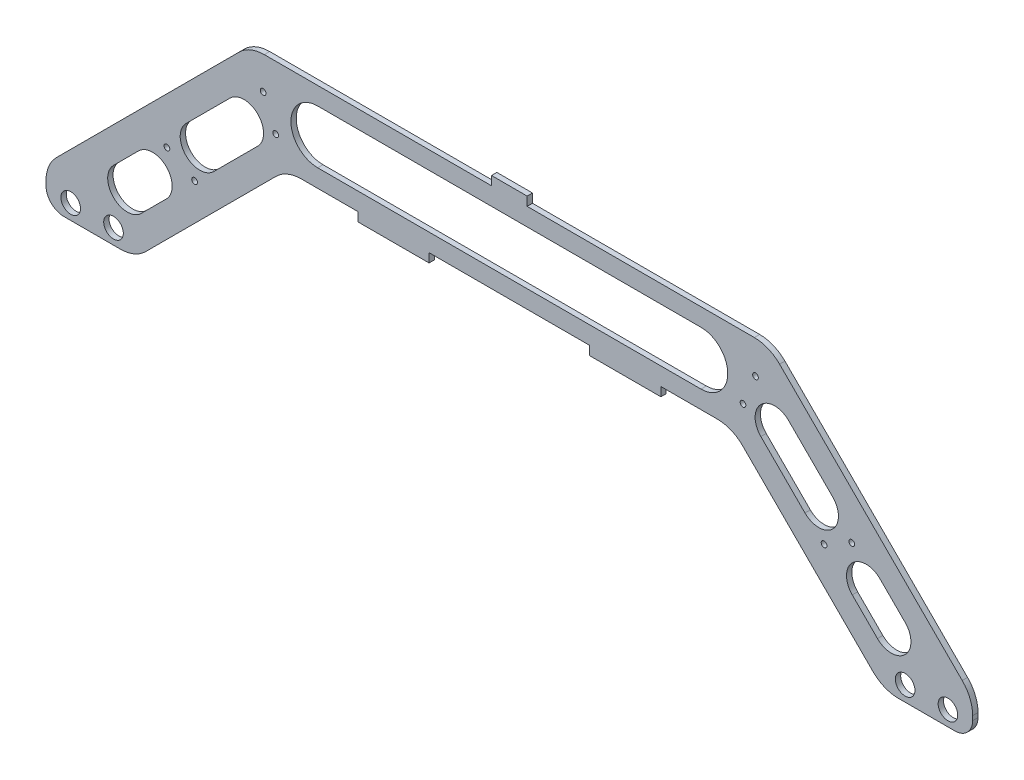
SolidWorks part; units mm, degrees
ref_plane "前视基准面" through (0, 0, 0) normal (0, 0, 1) x (1, 0, 0)
ref_plane "上视基准面" through (0, 0, 0) normal (0, 1, 0) x (1, 0, 0)
ref_plane "右视基准面" through (0, 0, 0) normal (1, 0, 0) x (0, 0, -1)
sketch "草图1" plane through (0, 0, 0) normal (0, 0, 1) x (1, 0, 0)
  line L0 (-125, 25) -> (-10, 25)
  line L1 (-125, 25) -> (-125, -25) construction
  line L2 (125, 25) -> (125, -25) construction
  line L3 (-116.7157, -25) -> (-85, -25)
  line L4 (-125, 25) -> (125, -25) construction
  line L5 (125, 25) -> (-125, -25) construction
  line L6 (0, 25) -> (0, 30) construction
  line L7 (-10, 25) -> (-10, 30)
  line L9 (-10, 30) -> (10, 30)
  line L10 (10, 25) -> (10, 30)
  line L11 (0, 25) -> (10, 30) construction
  line L12 (-10, 30) -> (0, 25) construction
  line L13 (-130.8579, -30.8579) -> (-203.9949, -103.9949)
  line L19 (10, 25) -> (125, 25)
  line L20 (-167.4264, -67.4264) -> (-202.7817, -32.0711) construction
  line L21 (125, 25) -> (125, -25) construction
  line L22 (-202.7817, -32.0711) -> (-151.5685, 19.1421)
  line L23 (-137.4264, 25) -> (-125, 25)
  line L24 (-202.7817, -32.0711) -> (-253.9949, -83.2843)
  line L25 (-259.8528, -97.4264) -> (-259.8528, -99.8528)
  line L26 (259.8528, -97.4264) -> (259.8528, -99.8528)
  line L27 (202.7817, -32.0711) -> (253.9949, -83.2843)
  line L28 (137.4264, 25) -> (125, 25)
  line L29 (202.7817, -32.0711) -> (151.5685, 19.1421)
  line L30 (167.4264, -67.4264) -> (202.7817, -32.0711) construction
  line L31 (218.1371, -109.8528) -> (249.8528, -109.8528)
  line L32 (130.8579, -30.8579) -> (203.9949, -103.9949)
  line L33 (-249.8528, -109.8528) -> (-218.1371, -109.8528)
  line L34 (-233.9949, -109.8528) -> (-233.9949, -63.2843) construction
  line L35 (-233.9949, -109.8528) -> (-245.9949, -109.8528)
  line L36 (-245.9949, -109.8528) -> (-245.9949, -101.3528)
  line L37 (-245.9949, -101.3528) -> (-245.9949, -106.8528)
  line L38 (-125, -25) -> (-85, -25) construction
  line L39 (0, -25) -> (-45, -25)
  line L40 (-65, -25) -> (-65, -30)
  line L41 (-85, -30) -> (-45, -30)
  line L42 (-85, -30) -> (-85, -25)
  line L43 (-45, -30) -> (-45, -25)
  line L44 (45, -30) -> (45, -25)
  line L45 (85, -30) -> (85, -25)
  line L46 (85, -30) -> (45, -30)
  line L47 (65, -25) -> (65, -30)
  line L48 (-45, -25) -> (45, -25)
  line L49 (-45, -25) -> (45, -25) construction
  line L50 (85, -25) -> (116.7157, -25)
  line L51 (85, -25) -> (125, -25) construction
  arc A0 (-249.8528, -109.8528) -> (-259.8528, -99.8528) centre (-249.8528, -99.8528) cw
  arc A1 (-116.7157, -25) -> (-130.8579, -30.8579) centre (-116.7157, -45) ccw
  arc A2 (-137.4264, 25) -> (-151.5685, 19.1421) centre (-137.4264, 5) ccw
  arc A3 (-253.9949, -83.2843) -> (-259.8528, -97.4264) centre (-239.8528, -97.4264) ccw
  arc A4 (-203.9949, -103.9949) -> (-218.1371, -109.8528) centre (-218.1371, -89.8528) cw
  arc A5 (203.9949, -103.9949) -> (218.1371, -109.8528) centre (218.1371, -89.8528) ccw
  arc A6 (253.9949, -83.2843) -> (259.8528, -97.4264) centre (239.8528, -97.4264) cw
  arc A7 (137.4264, 25) -> (151.5685, 19.1421) centre (137.4264, 5) cw
  arc A8 (116.7157, -25) -> (130.8579, -30.8579) centre (116.7157, -45) cw
  arc A9 (249.8528, -109.8528) -> (259.8528, -99.8528) centre (249.8528, -99.8528) ccw
  circle A12 centre (-245.9949, -101.3528) radius 5.5
  circle A13 centre (-221.9949, -101.3528) radius 5.5
  circle A14 centre (221.9949, -101.3528) radius 5.5
  circle A15 centre (245.9949, -101.3528) radius 5.5
  point P1 (0, 0)
  point P20 (-259.8528, -109.8528)
  point P30 (-209.8528, -109.8528)
  point P48 (209.8528, -109.8528)
  point P49 (259.8528, -109.8528)
  point P68 (-65, -30)
  point P76 (65, -30)
  dimension "D7" = 10
  dimension "D8" = 20
  dimension "D11" = 5.5
  dimension "D12" = 65
  dimension "D1" = 250
  dimension "D2" = 50
  dimension "D3" = 5
  dimension "D4" = 50
  dimension "D5" = 120
  dimension "D6" = 50
  dimension "D9" = 12
  dimension "D10" = 8.5
  dimension "D13" = 5
  dimension "D14" = 20
extrude "凸台-拉伸1" add sketch "草图1" along normal mid plane 3 contours A12 L33 A4 L13 A1 L3 A8 L32 A5 L31 A9 L26 A6 L27 L29 A7 L28 L19 L10 L9 L7 L0 L23 A2 L22 L24 A3 L25 A0 A13 A14 A15 region at (-67.5, 19.6181, 0)
sketch "草图2" plane through (0, 0, 1.5) normal (0, 0, 1) x (1, 0, 0)
  line L0 (-107.5, 0) -> (107.5, 0) construction
  line L1 (-158.1371, 55) -> (-116.7157, -45)
  line L2 (-107.5, 15) -> (107.5, 15)
  line L3 (-107.5, -15) -> (107.5, -15)
  line L4 (-221.9949, -101.3528) -> (-245.9949, -101.3528)
  line L5 (-245.9949, -101.3528) -> (-138.0754, 6.5668) construction
  line L6 (-221.9949, -101.3528) -> (-131.0459, -10.4038) construction
  line L7 (0, -15) -> (0, 15) construction
  line L8 (-228.3883, -57.6777) -> (-193.033, -93.033)
  line L9 (-202.7817, -32.0711) -> (-253.9949, -83.2843) construction
  line L10 (-130.8579, -30.8579) -> (-203.9949, -103.9949) construction
  line L11 (-210.7107, -75.3553) -> (-161.2132, -25.8579)
  line L12 (-148.8388, -13.4835) -> (-173.5876, -38.2322) construction
  line L13 (-210.7107, -75.3553) -> (-207.1751, -71.8198)
  line L14 (-141.0607, -21.2617) -> (-165.8094, -46.0104)
  line L15 (-156.617, -5.7053) -> (-181.3657, -30.4541)
  line L16 (-214.2462, -78.8909) -> (-200.1041, -64.7487) construction
  line L17 (148.8388, -13.4835) -> (173.5876, -38.2322) construction
  line L18 (-222.0244, -71.1127) -> (-207.8823, -56.9706)
  line L19 (-206.468, -86.669) -> (-192.3259, -72.5269)
  line L20 (141.0607, -21.2617) -> (165.8094, -46.0104)
  line L21 (156.617, -5.7053) -> (181.3657, -30.4541)
  line L22 (214.2462, -78.8909) -> (200.1041, -64.7487) construction
  line L23 (222.0244, -71.1127) -> (207.8823, -56.9706)
  line L24 (206.468, -86.669) -> (192.3259, -72.5269)
  arc A0 (-107.5, 15) -> (-107.5, -15) centre (-107.5, 0) ccw
  arc A1 (107.5, -15) -> (107.5, 15) centre (107.5, 0) ccw
  circle A2 centre (-138.0754, 6.5668) radius 1.6
  circle A3 centre (-131.0459, -10.4038) radius 1.6
  circle A6 centre (-176.5204, -55.8783) radius 1.6
  circle A7 centre (-192.0352, -47.393) radius 1.6
  circle A8 centre (131.0459, -10.4038) radius 1.6
  circle A9 centre (138.0754, 6.5668) radius 1.6
  circle A10 centre (176.5204, -55.8783) radius 1.6
  circle A11 centre (192.0352, -47.393) radius 1.6
  arc A12 (-141.0607, -21.2617) -> (-156.617, -5.7053) centre (-148.8388, -13.4835) ccw
  arc A13 (-181.3657, -30.4541) -> (-165.8094, -46.0104) centre (-173.5876, -38.2322) ccw
  arc A14 (-222.0244, -71.1127) -> (-206.468, -86.669) centre (-214.2462, -78.8909) ccw
  arc A15 (-192.3259, -72.5269) -> (-207.8823, -56.9706) centre (-200.1041, -64.7487) ccw
  arc A16 (141.0607, -21.2617) -> (156.617, -5.7053) centre (148.8388, -13.4835) cw
  arc A17 (181.3657, -30.4541) -> (165.8094, -46.0104) centre (173.5876, -38.2322) cw
  arc A18 (222.0244, -71.1127) -> (206.468, -86.669) centre (214.2462, -78.8909) cw
  arc A19 (192.3259, -72.5269) -> (207.8823, -56.9706) centre (200.1041, -64.7487) cw
  point P5 (0, 0)
  point P17 (-137.4264, 5)
  point P50 (-207.1751, -71.8198)
  point P51 (-161.2132, -25.8579)
  point P60 (161.2132, -25.8579)
  point P67 (207.1751, -71.8198)
  dimension "D1" = 3.2
  dimension "D2" = 3.2
  dimension "D3" = 3.2
  dimension "D4" = 3.2
  dimension "D5" = 70
  dimension "D6" = 5
extrude "切除-拉伸6" cut sketch "草图2" against normal through all contours L3 A1 L2 A0 region at (0, 0, 1.5)
extrude "切除-拉伸7" cut sketch "草图2<5>" against normal through all contours A7 | A6 | A2 | A3 | A9 | A8 | A11 | A10 | L19 A15 L18 A14 | A12 L15 A13 L14 | L21 A17 L20 A16 | L23 A19 L24 A18
sketch "草图2<5>" plane through (0, 0, 1.5) normal (0, 0, 1) x (1, 0, 0) same geometry as "草图2"
